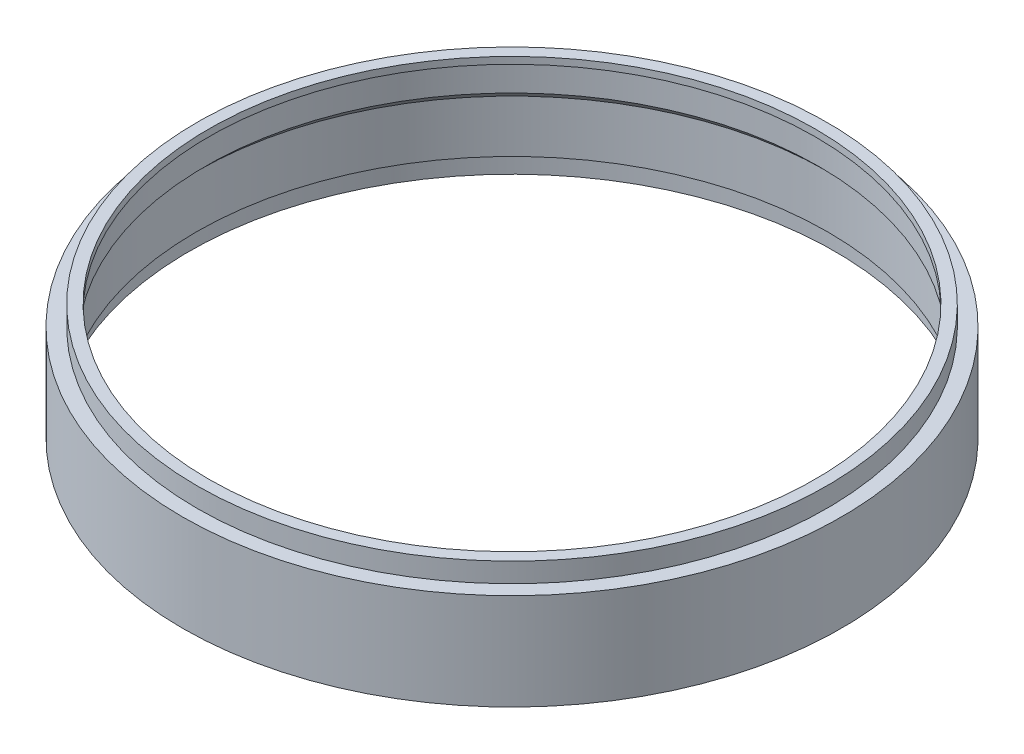
SolidWorks part; units mm, degrees
ref_plane "Front Plane" through (0, 0, 0) normal (0, 0, 1) x (1, 0, 0)
ref_plane "Top Plane" through (0, 0, 0) normal (0, 1, 0) x (1, 0, 0)
ref_plane "Right Plane" through (0, 0, 0) normal (1, 0, 0) x (0, 0, -1)
ref_axis "Axis1" through (0, 0, 0) along (0, 1, 0)
sketch "Sketch1" plane through (0, 0, 0) normal (0, 0, 1) x (1, 0, 0)
  line L0 (0, 0) -> (0, -50000) construction
  line L1 (-48.35, 0) -> (-48.35, 14.15)
  line L2 (-48.35, 0) -> (-47.4, 0)
  line L3 (-47.4, 0) -> (-47.4, 3)
  line L4 (-47.4, 3) -> (-46.35, 3)
  line L5 (-46.35, 3) -> (-46.35, 10.67)
  line L7 (-48.35, 0) -> (-48.35, -9.6235) construction
  line L8 (-46.35, 10.67) -> (-45, 12.02)
  line L10 (-45, 12.02) -> (-45, 16.02)
  line L11 (-45, 16.02) -> (-44.5, 16.02)
  line L12 (-47.35, 3) -> (-47.35, 0) construction
  line L13 (-46.35, 3) -> (-46.35, -7.15) construction
  line L17 (-44.5, 16.02) -> (-44.5, 17.02)
  line L26 (-46.2, 17.02) -> (-46.2, 14.15)
  line L27 (-46.2, 14.15) -> (-48.35, 14.15)
  line L31 (46.35, 3) -> (-46.35, 3) construction
  line L32 (-46.2, 17.02) -> (-44.5, 17.02)
  line L34 (-48.35, 15.15) -> (48.35, 15.15) construction
  dimension "D1" = 135
  dimension "D2" = 90
  dimension "D3" = 1.2
  dimension "D4" = 0.5
  dimension "D5" = 1
  dimension "D6" = 0.05
  dimension "D7" = 4
  dimension "D8" = 1
revolve "Revolve1" add sketch "Sketch1" angle 360 about L0
